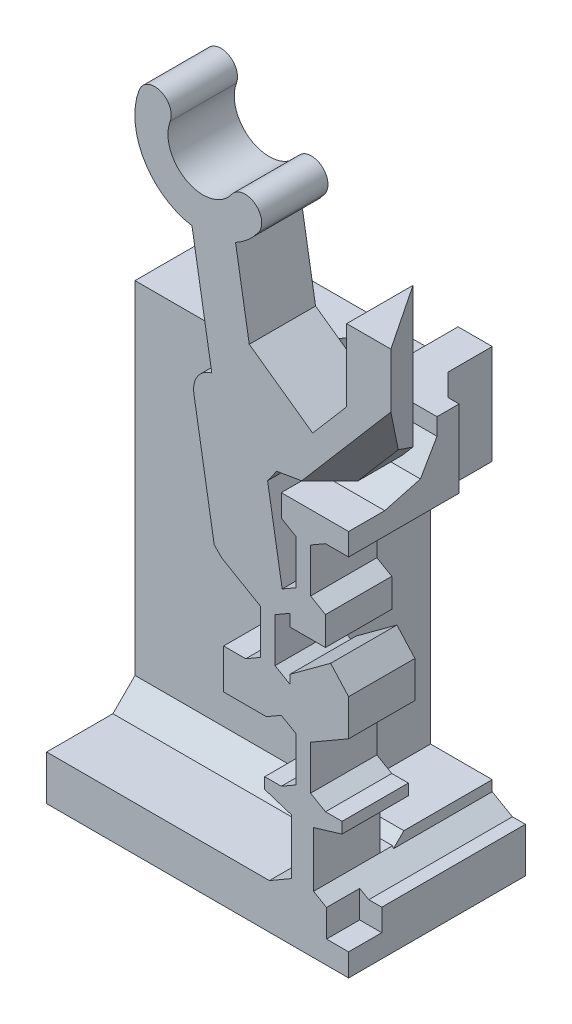
SolidWorks part; units mm, degrees
material "Nylon 6/12"
ref_plane "Front Plane" through (0, 0, 0) normal (0, 0, 1) x (1, 0, 0)
ref_plane "Top Plane" through (0, 0, 0) normal (0, 1, 0) x (1, 0, 0)
ref_plane "Right Plane" through (0, 0, 0) normal (1, 0, 0) x (0, 0, -1)
sketch "Sketch-SkeletonConfigUp" plane through (0, 0, 0) normal (0, 0, 1) x (1, 0, 0)
  line L0 (0, 0) -> (0, -50000) construction
  line L1 (0, 0) -> (4.5811, 6.2164) construction
  line L2 (9.8143, 13.3177) -> (4.5811, 13.945) construction
  line L3 (4.5811, 13.945) -> (2.9713, 10.4094) construction
  line L4 (2.9713, 10.4094) -> (4.5811, 6.2164) construction
  line L5 (4.5811, 13.945) -> (6.2429, 19.1409) construction
  line L6 (2.9713, 10.4094) -> (0.0405, 27.8193) construction
  line L7 (4.5811, 6.2164) -> (9.8143, 13.3177) construction
  line L8 (-587.3593, -797.0242) -> (9.8143, 13.3177) construction
  dimension "D2" = 7.7221
  dimension "D3" = 8.8212
  dimension "D4" = 5.2707
  dimension "D5" = 119.553
  dimension "D6" = 3.8848
  dimension "D7" = 5.4552
  dimension "D8" = 17.6549
  dimension "D9" = 4.4914
  dimension "D10" = 6.745
  dimension "D11" = 145.964
  dimension "D12" = 143.612
sketch "Sketch-SkeletonConfigDown" plane through (0, 0, 0) normal (0, 0, 1) x (1, 0, 0)
  line L0 (0, 0) -> (0, -50000) construction
  line L1 (0, 0) -> (4.5811, 6.2164) construction
  line L2 (9.8143, 13.3177) -> (4.5811, 13.945) construction
  line L3 (4.5811, 13.945) -> (6.1909, 10.4094) construction
  line L4 (6.1909, 10.4094) -> (4.5811, 6.2164) construction
  line L5 (4.5811, 13.945) -> (1.753, 18.6098) construction
  line L6 (6.1909, 10.4094) -> (-8.8652, 19.6294) construction
  line L7 (4.5811, 6.2164) -> (9.8143, 13.3177) construction
  line L8 (-589.9357, -800.5203) -> (9.8143, 13.3177) construction
  dimension "D2" = 7.7221
  dimension "D3" = 8.8212
  dimension "D4" = 5.2707
  dimension "D5" = 119.553
  dimension "D6" = 3.8848
  dimension "D7" = 5.4552
  dimension "D8" = 17.6549
  dimension "D9" = 4.4914
  dimension "D10" = 6.745
  dimension "D11" = 145.964
  dimension "D1" = 143.612
ref_plane "Plane-Cam Base" through (9.128, 0, 0) normal (1, 0, 0) x (0, 0, -1)
ref_plane "Plane-Down-to-Up Derailleur Clearance" through (6.628, 0, 0) normal (1, 0, 0) x (0, 0, -1)
ref_plane "Plane-Cam Cavity Roof" through (5.128, 0, 0) normal (1, 0, 0) x (0, 0, -1)
sketch "Sketch-SwitchBossUp" plane through (0, 0, 0) normal (0, 0, 1) x (1, 0, 0)
  line L0 (3.5811, 11.4759) -> (3.5811, 12.945) construction
  line L2 (6.5405, 21.1774) -> (6.5405, 24.4384)
  line L3 (6.5405, 24.4384) -> (8.5405, 24.4384)
  line L4 (8.5405, 24.4384) -> (8.5405, 20.4384)
  line L5 (5.5811, 12.5552) -> (5.5811, 11.263)
  line L7 (1.5115, 25.1048) -> (2.5464, 18.9575)
  line L8 (-0.4607, 24.7728) -> (0.4359, 19.4465)
  line L9 (2.9713, 10.4094) -> (0.0405, 27.8193) construction
  line L11 (-0.0396, 22.2712) -> (1.9326, 22.6032) construction
  line L15 (6.628, -23.7286) -> (6.628, 23.7286) construction
  line L16 (2.9713, 10.4094) -> (4.5811, 6.2164) construction
  line L17 (3.5811, 12.945) -> (3.5811, 14.945) construction
  line L18 (5.5811, 12.945) -> (5.5811, 14.945) construction
  line L19 (4.2561, 13.945) -> (4.9061, 13.945) construction
  line L20 (3.5811, 14.945) -> (5.5811, 14.945) construction
  line L21 (3.5811, 12.945) -> (5.5811, 12.945) construction
  line L22 (4.5811, 12.945) -> (4.5811, 14.945) construction
  line L23 (4.5811, 6.2164) -> (8.5405, 7.1023) construction
  line L24 (1.9713, 9.4094) -> (1.9713, 11.4094) construction
  line L25 (3.9713, 9.4094) -> (3.9713, 11.4094) construction
  line L26 (3.9713, 9.4094) -> (1.9713, 9.4094) construction
  line L27 (1.9713, 11.4094) -> (3.9713, 11.4094) construction
  line L28 (3.5811, 7.2164) -> (5.5811, 7.2164) construction
  line L29 (3.5811, 7.2164) -> (3.5811, 5.2164) construction
  line L30 (5.5811, 7.2164) -> (5.5811, 5.2164) construction
  line L31 (3.5811, 5.2164) -> (5.5811, 5.2164) construction
  line L32 (4.9061, 6.2164) -> (4.2561, 6.2164) construction
  line L40 (3.2963, 10.4094) -> (2.6463, 10.4094) construction
  line L43 (2.874, 4.5093) -> (0.7934, 4.5093) construction
  line L46 (5.0405, 1.437) -> (5.0405, 3.937)
  line L51 (4.9929, 19.3693) -> (2.5464, 18.9575)
  line L66 (0.0405, 27.8193) -> (0.0405, 50027.8193) construction
  line L74 (0.5455, 12.7717) -> (-0.3728, 18.2264)
  line L75 (0.3841, 13.7302) -> (2.3564, 14.0622) construction
  line L76 (5.5811, 11.263) -> (5.5811, 12.5552) construction
  line L77 (5.5811, 7.6061) -> (6.628, 8.2105)
  line L80 (5.8152, 10.763) -> (6.628, 9.8603)
  line L81 (8.5405, 1033.6218) -> (8.5405, 20.4384) construction
  line L82 (2.5464, 18.9575) -> (3.5585, 12.945) construction
  line L83 (3.6203, 12.5779) -> (2.8784, 16.9852)
  line L84 (2.8784, 16.9852) -> (6.0405, 17.5175)
  line L85 (6.9307, 9.5241) -> (8.5405, 7.7363) construction
  line L88 (3.5811, 16.3347) -> (6.8573, 16.3347)
  line L92 (3.7762, 8.3129) -> (6.9307, 9.5241) construction
  line L93 (6.3311, 4.3267) -> (5.0405, 3.937)
  line L95 (2.5464, 18.9575) -> (2.8784, 16.9852) construction
  line L96 (2.7124, 17.9713) -> (8.5405, 18.9524) construction
  line L97 (2.7124, 17.9713) -> (1.7262, 17.8053) construction
  line L98 (1.9713, 9.0197) -> (0.9713, 9.0197)
  line L99 (0.9713, 9.0197) -> (0.9713, 7.2164)
  line L100 (0.9713, 7.2164) -> (2.9061, 7.2164)
  line L101 (4.5811, 6.2164) -> (6.9307, 9.5241) construction
  line L103 (0.0405, 27.8193) -> (1.9448, 26.4638) construction
  line L104 (6.9307, 9.5241) -> (8.5405, 7.7363) construction
  line L106 (13.4416, 14.945) -> (5.5811, 14.945) construction
  line L107 (1.9713, 9.4094) -> (1.9713, 9.0197) construction
  line L109 (0.0405, 27.8193) -> (-2.1498, 28.6358) construction
  line L110 (8.5405, 20.4384) -> (6.0405, 17.5175)
  line L111 (6.628, 9.8603) -> (6.628, 8.2105)
  line L112 (6.628, 9.8603) -> (6.9307, 9.5241) construction
  line L113 (2.8311, 4.8267) -> (2.8311, 4.3267)
  line L114 (7.3693, 7.7363) -> (7.3563, 7.7363) construction
  line L115 (6.8573, 16.3347) -> (13.4416, 16.3347)
  line L116 (13.4416, 16.3347) -> (13.4416, -1.1653)
  line L117 (13.4416, -1.1653) -> (5.0405, -1.1653)
  line L119 (10.4375, 14.0252) -> (10.4375, 2.1692)
  line L121 (5.0405, -1.1653) -> (5.0405, 1.437) construction
  line L122 (8.237, 12.8031) -> (10.8393, 12.8031) construction
  line L123 (10.8393, 12.8031) -> (13.4416, 12.8031) construction
  line L124 (10.4375, 2.1692) -> (9.128, 0.8597)
  line L125 (8.5405, 7.5847) -> (13.4416, 7.5847) construction
  line L127 (5.5811, 15.3347) -> (5.5811, 14.945) construction
  line L130 (6.0405, 0.8597) -> (9.128, 0.8597)
  line L132 (2.8311, 4.3267) -> (4.0405, 3.937)
  line L133 (2.9713, 10.4094) -> (6.1909, 10.4094) construction
  line L134 (4.5811, 10.4094) -> (4.5811, 13.945) construction
  line L135 (4.5811, 10.4094) -> (4.5811, 6.2164) construction
  line L136 (0.8973, 12.4192) -> (0.5455, 12.7717)
  line L137 (3.9713, 9.4094) -> (5.5811, 7.2164) construction
  line L139 (5.8152, 10.763) -> (3.9713, 9.4094)
  line L140 (4.0405, 3.937) -> (4.0405, 1.437)
  line L141 (4.0405, 1.437) -> (3.0405, 0.8597)
  line L142 (3.0405, 0.8597) -> (3.0405, -1.1653)
  line L143 (8.5405, 20.4384) -> (8.5405, 18.9524) construction
  line L145 (8.5405, 17.9384) -> (8.5405, -49992.0368) construction
  line L147 (5.5811, 11.263) -> (5.5811, 12.5552) construction
  line L149 (6.3311, 4.8267) -> (6.3311, 4.3267)
  line L150 (3.0405, -1.1653) -> (5.0405, -1.1653)
  line L151 (4.0405, 3.937) -> (5.0405, 3.937) construction
  line L152 (4.2561, 14.945) -> (4.2561, 12.945)
  line L153 (4.9061, 14.945) -> (4.9061, 12.945)
  line L155 (4.2561, 14.945) -> (3.5811, 15.3347)
  line L156 (4.9061, 14.945) -> (5.5811, 15.3347)
  line L157 (3.5811, 16.3347) -> (3.5811, 15.3347)
  line L158 (5.5811, 15.3347) -> (9.128, 15.3347)
  line L162 (3.2963, 11.4094) -> (3.2963, 9.4094)
  line L164 (2.6463, 11.4094) -> (2.6463, 9.4094)
  line L169 (4.2561, 7.2164) -> (4.2561, 5.2164)
  line L170 (4.9061, 5.2164) -> (4.9061, 7.2164)
  line L175 (4.2561, 7.2164) -> (3.5811, 7.6061)
  line L176 (4.9061, 7.2164) -> (5.5811, 7.6061)
  line L177 (5.5811, 7.2164) -> (5.5811, 7.6061) construction
  line L179 (4.2561, 5.2164) -> (3.5811, 4.8267)
  line L180 (3.5811, 5.2164) -> (3.5811, 4.8267) construction
  line L181 (3.5811, 4.8267) -> (2.8311, 4.8267)
  line L183 (4.9061, 5.2164) -> (5.5811, 4.8267)
  line L184 (5.5811, 5.2164) -> (5.5811, 4.8267) construction
  line L186 (9.128, -23.7286) -> (9.128, 23.7286) construction
  line L187 (2.6463, 9.4094) -> (1.9713, 9.0197)
  line L188 (3.2963, 9.4094) -> (3.9713, 9.0197)
  line L189 (3.2963, 11.4094) -> (3.9713, 11.7991)
  line L190 (2.6463, 11.4094) -> (0.8973, 12.4192)
  line L191 (3.9713, 11.4094) -> (3.9713, 11.7991) construction
  line L192 (3.9713, 11.7991) -> (3.9713, 11.263)
  line L193 (4.9061, 12.945) -> (5.5811, 12.5552)
  line L194 (4.2561, 12.945) -> (3.6203, 12.5779)
  line L195 (3.9713, 11.263) -> (5.5811, 11.263)
  line L196 (3.9713, 9.4094) -> (3.9713, 9.0197)
  line L197 (3.5811, 7.2164) -> (3.5811, 7.6061) construction
  line L199 (3.5811, 7.6061) -> (2.9061, 7.2164)
  line L200 (5.5811, 4.8267) -> (6.3311, 4.8267)
  line L201 (2.8311, 4.3267) -> (2.8311, 3.937) construction
  line L202 (2.8311, 3.937) -> (4.0405, 3.937) construction
  line L203 (10.4375, 14.0252) -> (9.128, 15.3347)
  line L204 (4.0405, 1.437) -> (3.0405, 1.437) construction
  line L205 (3.0405, 1.437) -> (3.0405, 0.8597) construction
  line L206 (5.0405, 1.437) -> (6.0405, 0.8597)
  line L207 (8.5405, 18.9524) -> (8.5405, 17.9384) construction
  line L208 (6.0405, 17.5175) -> (8.5405, 17.9384) construction
  line L209 (8.5405, 20.4384) -> (8.5405, 17.9384) construction
  line L210 (6.5405, 21.1774) -> (4.9929, 19.3693)
  arc A0 (1.5115, 25.1048) -> (2.5558, 26.0289) centre (0.0405, 27.8193) ccw
  arc A1 (-0.4607, 24.7728) -> (-2.8525, 28.8978) centre (0.0405, 27.8193) cw
  arc A2 (-2.8525, 28.8978) -> (-1.447, 28.3738) centre (-2.1498, 28.6358) cw
  arc A3 (2.5558, 26.0289) -> (1.3338, 26.8987) centre (1.9448, 26.4638) ccw
  arc A4 (-1.447, 28.3738) -> (1.3338, 26.8987) centre (0.0405, 27.8193) ccw
  arc A5 (3.5811, 12.945) -> (3.5811, 14.945) centre (3.1778, 13.945) ccw construction
  arc A6 (5.5811, 12.945) -> (5.5811, 14.945) centre (5.9843, 13.945) cw construction
  arc A7 (2.5293, 9.921) -> (1.9713, 11.4094) centre (1.568, 10.4094) ccw construction
  arc A8 (3.9713, 11.4094) -> (3.9713, 9.4094) centre (4.3745, 10.4094) ccw construction
  arc A9 (3.5811, 7.2164) -> (3.5811, 5.2164) centre (3.1779, 6.2164) cw construction
  arc A10 (5.5811, 7.2164) -> (5.5811, 5.2164) centre (5.9844, 6.2164) ccw construction
  arc A19 (-0.3728, 18.2264) -> (0.4359, 19.4465) centre (0.6836, 18.4042) cw
  circle A28 centre (0.0405, 27.8193) radius 2.3375 construction
  arc A29 (1.9713, 9.4094) -> (2.5293, 9.921) centre (1.568, 10.4094) ccw construction
  point P53 (4.5811, 13.945)
  point P63 (2.9713, 10.4094)
  point P93 (0.9465, 22.4372)
  dimension "D23" = 1.5875
  dimension "D24" = 0.75
  dimension "D2" = 2
  dimension "D5" = 2
  dimension "D6" = 0.65
  dimension "D8" = 42
  dimension "D7" = 2
  dimension "D10" = 5
  dimension "D11" = 8.5
  dimension "D14" = 7.5
  dimension "D4" = 3
  dimension "D16" = 42
  dimension "D12" = 1
  dimension "D13" = 2.5
  dimension "D25" = 120
  dimension "D26" = 120
  dimension "D27" = 120
  dimension "D28" = 120
  dimension "D29" = 120
  dimension "D30" = 120
  dimension "D31" = 120
  dimension "D32" = 120
  dimension "D33" = 120
  dimension "D34" = 120
  dimension "D35" = 120
  dimension "D36" = 120
  dimension "D17" = 0.5
  dimension "D20" = 3.5
  dimension "D21" = 1
  dimension "D18" = 45
  dimension "D9" = 17.5
  dimension "D22" = 1
  dimension "D19" = 120
  dimension "D37" = 120
  dimension "D15" = 45
  dimension "D38" = 2
  dimension "D39" = 0.5
  dimension "D40" = 60
  dimension "D41" = 1
  dimension "D42" = 45
  dimension "D43" = 120
  dimension "D44" = 2
  dimension "D45" = 2.5
  dimension "D46" = 2.5
  dimension "D47" = 4
  dimension "D48" = 2
extrude "Boss-Switch Main" add sketch "Sketch-SwitchBossUp" along normal blind 3
sketch "Sketch1" plane through (0, 0, 0) normal (0, 0, -1) x (-1, 0, 0)
  line L0 (-3.5811, 16.3347) -> (-3.5811, 15.3347) construction
  line L1 (-7.5811, -1.1653) -> (0.4122, -1.1653)
  line L2 (-7.5811, -1.1653) -> (-7.5811, 0.8597)
  line L4 (0.4122, -1.1653) -> (0.4122, 0.8597)
  line L5 (-3.5811, 18.8347) -> (-7.5811, 18.8347)
  line L10 (-7.5811, 18.8347) -> (-7.5811, 15.3347)
  line L11 (-4.0405, 1.437) -> (-5.0405, 1.437)
  line L12 (-7.5811, 15.3347) -> (-3.5811, 15.3347)
  line L13 (-4.0405, 1.437) -> (-3.0405, 0.8597)
  line L14 (-3.5811, 15.3347) -> (-3.5811, 18.8347)
  line L22 (-3.0405, -1.1653) -> (-13.4416, -1.1653) construction
  line L23 (-3.0405, 0.8597) -> (0.4122, 0.8597)
  line L24 (-5.0405, 1.437) -> (-6.0405, 0.8597)
  line L25 (-6.0405, 0.8597) -> (-7.5811, 0.8597)
  line L26 (-9.128, 15.3347) -> (-5.5811, 15.3347) construction
  dimension "D1" = 3.5
  dimension "D4" = 4
extrude "Boss-Flange Width" add sketch "Sketch1" along normal blind 5
ref_plane "Plane-Sta2Sit Groove" through (0.0405, 0, 0) normal (1, 0, 0) x (0, 0, -1)
ref_plane "Plane-Cam Outer Surface" through (-12.0395, 0, 0) normal (1, 0, 0) x (0, 0, -1)
ref_plane "Plane-FlangeTop" through (-7.0395, 0, 0) normal (1, 0, 0) x (0, 0, -1)
sketch "Sketch2" plane through (-7.0395, 0, 0) normal (1, 0, 0) x (0, 0, -1)
  line L0 (5, 15.3347) -> (0, 15.3347) construction
  line L1 (5, 17.3347) -> (1, 17.3347)
  line L2 (5, 17.3347) -> (5, 15.3347)
  line L3 (5, 15.3347) -> (1, 15.3347)
  line L4 (1, 17.3347) -> (1, 15.3347)
  line L10 (-3, -1.1653) -> (-3, 16.3347) construction
  line L11 (5, 0.8597) -> (-3, 0.8597)
  line L12 (5, 0.8597) -> (5, -1.1653)
  line L13 (5, -1.1653) -> (-3, -1.1653)
  line L14 (-3, 0.8597) -> (-3, -1.1653)
  line L15 (0, 10.4094) -> (0, 27.8193) construction
  line L17 (5, 0.8597) -> (5, -1.1653) construction
  line L18 (-3, 0.8597) -> (0, 0.8597) construction
  dimension "D1" = 1
  dimension "D2" = 2
extrude "Boss-Flange Height" add sketch "Sketch2" along normal up to surface (11.6675 mm away)
sketch "Sketch10" plane through (0, 15.3347, 0) normal (0, 1, 0) x (1, 0, 0)
  line L0 (9.128, -23.7286) -> (9.128, 23.7286) construction
  line L1 (7.5811, 5) -> (5.128, 5)
  line L2 (7.5811, 5) -> (7.5811, 2)
  line L3 (7.5811, 2) -> (5.128, 2)
  line L5 (4.628, 7) -> (4.628, 1) construction
  line L6 (3.5811, 1) -> (-7.0395, 1) construction
  line L8 (5.128, 5) -> (5.128, 2)
  dimension "D1" = 1
  dimension "D2" = 0.5
  dimension "D3" = 4.5
extrude "Cut-Up-To-Down Derailleur Clearance" cut sketch "Sketch10" along normal up to next
sketch "Sketch17" plane through (0, 15.3347, 0) normal (0, -1, 0) x (1, 0, 0)
  line L0 (5.128, -5) -> (-7.0395, -5)
  line L1 (5.128, -5) -> (3.5811, -5) construction
  line L2 (-7.0395, -5) -> (-7.0395, -1)
  line L3 (-7.0395, -1) -> (5.128, -1)
  line L4 (5.128, -1) -> (5.128, -5)
  line L5 (-7.0395, -1) -> (-7.0395, -5) construction
extrude "Boss-Flange Support" add sketch "Sketch17" along normal up to surface (14.475 mm away) up to face at (-1.9995, 0.8597, -1)
sketch "Sketch-HolePositions" plane through (0, -1.1653, 0) normal (0, -1, 0) x (1, 0, 0)
  line L0 (-7.0395, -3) -> (7.5811, -3) construction
  line L1 (7.5811, -5) -> (-7.0395, -5) construction
  line L2 (7.5811, -5) -> (7.5811, 0) construction
  line L4 (-7.0395, -22.2167) -> (-7.0395, 22.2167) construction
  line L5 (3.5811, -1) -> (3.5811, -5) construction
  point P6 (-4.0395, -3)
  point P7 (0.5811, -3)
  dimension "D1" = 3
  dimension "D2" = 3
  dimension "D3" = 2
sketch "Sketch6" plane through (0, -1.1653, 0) normal (0, -1, 0) x (-1, 0, 0)
  point P0 (4.0395, 3)
  point P3 (-0.5811, 3)
hole_wizard "Tap Drill for M2x0.4 Tap1" positions "Sketch6" profile "Sketch5" hole size "M2x0.4" standard "ANSI Metric" end condition through all
sketch "Sketch5" plane through (-4.0395, -1.1653, -3) normal (1, 0, 0) x (0, 0, -1)
  line L0 (0, 0) -> (0, 30.5511)
  line L1 (0, 30.5511) -> (0.8, 30.5511)
  line L2 (0.8, 30.5511) -> (0.8, 0)
  line L5 (0.8, 0) -> (0, 0)
  line L11 (0, -6.35) -> (0, 107.95) construction
  dimension "Thru Hole Dia." = 1.6
  dimension "Thru Hole Depth" = 30.5511
sketch "Sketch9" plane through (0, -1.1653, 0) normal (0, -1, 0) x (1, 0, 0)
  point P0 (-4.0395, -3)
  point P3 (0.5811, -3)
hole_wizard "M2 Clearance Hole2" positions "Sketch9" profile "Sketch8" hole size "M2" standard "ANSI Metric"
sketch "Sketch8" plane through (-4.0395, -1.1653, -3) normal (1, 0, 0) x (0, 0, -1)
  line L0 (0, 0) -> (0, 15.721)
  line L1 (0, 15.721) -> (1.2, 15)
  line L2 (1.2, 15) -> (1.2, 0)
  line L5 (1.2, 0) -> (0, 0)
  line L10 (0, 15.721) -> (-1.2, 15) construction
  line L11 (0, -6.35) -> (0, 107.95) construction
  dimension "Hole Dia." = 2.4
  dimension "Hole Depth" = 15
  dimension "Drill Angle" = 118
sketch "Sketch-Measurements for Derailleur Ramps" plane through (0, 0, 0) normal (0, 0, 1) x (1, 0, 0)
  line L0 (2.8784, 16.9852) -> (2.5464, 18.9575)
  line L1 (2.7124, 17.9713) -> (1.7262, 17.8053)
  line L2 (2.9713, 10.4094) -> (0.0405, 27.8193) construction
  line L3 (1.7262, 17.8053) -> (-1.8937, 15.3603)
  line L4 (6.1909, 10.4094) -> (-8.8652, 19.6294) construction
  line L5 (1.7262, 17.8053) -> (2.6012, 12.6077)
  line L6 (2.6012, 12.6077) -> (-1.8937, 15.3603)
  line L7 (-0.0837, 16.5828) -> (-0.0837, 17.8053)
  line L8 (-0.0837, 17.8053) -> (1.7262, 17.8053)
  line L9 (6.1909, 10.4094) -> (2.9713, 10.4094)
  line L10 (5.386, 8.3129) -> (3.7762, 8.3129)
  line L12 (6.1909, 10.4094) -> (4.5811, 6.2164) construction
  line L13 (4.5811, 8.3129) -> (4.5811, 8.7912)
  line L14 (4.5811, 6.2164) -> (5.386, 8.3129)
  line L15 (2.9713, 10.4094) -> (4.5811, 6.2164) construction
  line L16 (3.7762, 8.3129) -> (4.5811, 6.2164)
  line L17 (5.386, 8.3129) -> (5.386, 8.7912)
  dimension "D1" = 1.81
  dimension "D2" = 0.8049
sketch "Sketch12" plane through (0, 24.4384, 0) normal (0, 1, 0) x (1, 0, 0)
  line L0 (6.5405, 0) -> (8.5405, -3)
  line L1 (8.5405, -3) -> (8.5405, 0)
  line L2 (8.5405, 0) -> (6.5405, 0)
extrude "Cut-Up-to-Down Cantilever Slope" cut sketch "Sketch12" against normal up to next
ref_plane "Plane1" through (0, 7.1023, 0) normal (0, 1, 0) x (1, 0, 0)
sketch "Sketch-Derailleur Location" plane through (0, 7.1023, 0) normal (0, 1, 0) x (1, 0, 0)
  line L0 (8.5405, 0) -> (8.5405, -3)
  line L1 (4.0405, -3) -> (3.0405, -3) construction
  line L2 (-119237.4187, 0) -> (9.8143, 0) construction
  point P0 (8.5405, 0)
  point P8 (8.5405, -1.5)
ref_plane "Plane-Cantilever Cut" [suppressed] through (7.0848, 8.5204, -1.9058) normal (-0.6301, -0.7578, 0.1695) x (-0.7765, 0.6151, -0.1368)
sketch "Sketch14" [suppressed] plane through (7.0848, 8.5204, -1.9058) normal (-0.6301, -0.7578, 0.1695) x (-0.7765, 0.6151, -0.1368)
  line L0 (2.3023, -1.6911) -> (-0.3551, -1.6911)
  line L2 (2.3023, -4.3362) -> (2.3023, -1.6911)
  line L3 (-0.3551, -1.6911) -> (-0.3551, -4.4608)
  line L5 (-0.3551, -4.4608) -> (1.0087, -5.0843)
  line L6 (1.0087, -5.0843) -> (2.3023, -4.3362)
extrude "Cut-Down-to-Up Cantilever Slope" [suppressed] cut sketch "Sketch14" against normal up to next
sketch "Sketch16" plane through (0, 0, 0) normal (0, 0, -1) x (-1, 0, 0)
  line L0 (-7.5811, 18.8347) -> (-13.4416, 18.8347)
  line L1 (-13.4416, 18.8347) -> (-13.4416, -1.1653)
  line L2 (-13.4416, -1.1653) -> (-6.628, -1.1653)
  line L3 (-13.4416, -1.1653) -> (-5.0405, -1.1653) construction
  line L4 (-6.628, -1.1653) -> (-6.628, 5.2038)
  line L5 (-6.628, 5.2038) -> (-8.0037, 5.2038)
  line L6 (-8.0037, 5.2038) -> (-8.0037, 12.0484)
  line L7 (-8.0037, 12.0484) -> (-6.628, 12.0484)
  line L8 (-6.628, 12.0484) -> (-6.628, 17.9477)
  line L9 (-6.628, 23.7286) -> (-6.628, -23.7286) construction
  line L10 (-3.5811, 18.8347) -> (-6.5405, 18.8347) construction
  line L11 (-7.5811, 18.8347) -> (-6.628, 17.9477)
extrude "Cut-Down-to-Up Derailleur Clearance" cut sketch "Sketch16" against normal through all and the other way through all
ref_plane "Plane-Symmetry Plane" through (0, 0, 1.5) normal (0, 0, 1) x (1, 0, 0)
sketch "Sketch-Cable Center Point" plane through (0, 0, 1.5) normal (0, 0, 1) x (1, 0, 0)
  line L0 (0.0405, 27.8193) -> (0.1722, 27.0366)
  line L1 (2.9713, 10.4094) -> (0.0405, 27.8193) construction
  point P0 (0.0405, 27.8193)
  dimension "D1" = 0.7937
chamfer "Chamfer-Flange Support" distance 1.5 angle 45 1 edges at (3.5811, 17.3347, -3)
chamfer "Chamfer-Flange Support 2" distance 1 angle 45 2 edges at (5.128, 17.0847, -2) (5.128, 15.3347, -1.5)
chamfer "Chamfer-Flange Support 3" distance 1 angle 45 1 edges at (-1.9995, 0.8597, -1)
sketch "Sketch18" plane through (6.628, 0, 0) normal (1, 0, 0) x (0, 0, -1)
  line L1 (-3, -0.1403) -> (-1.5, -0.1403)
  line L2 (-3, -0.1403) -> (-3, 1.437)
  line L3 (-3, 1.437) -> (-1.5, 1.437)
  line L4 (-1.5, -0.1403) -> (-1.5, 1.437)
  line L5 (0.5774, 1.437) -> (0, 1.437) construction
  line L6 (-3, -1.1653) -> (-3, 0.8597) construction
  line L7 (-3, 0.8597) -> (5, 0.8597) construction
  dimension "D1" = 1.5
  dimension "D2" = 1
extrude "Cut-Down-to-Up Derailleur Clearance 2" cut sketch "Sketch18" against normal blind 1
sketch "Sketch19" plane through (0, 0, 0) normal (0, 0, 1) x (1, 0, 0)
  line L7 (3.5811, 18.8347) -> (6.628, 18.8347)
  line L8 (6.628, 18.8347) -> (6.628, 16.3347)
  line L9 (6.628, 16.3347) -> (3.5811, 16.3347)
  line L10 (3.5811, 16.3347) -> (3.5811, 18.8347)
  line L11 (6.628, 16.3347) -> (6.628, 17.9477) construction
extrude "Cut-Up-to-Down Cantilever Clearance" cut sketch "Sketch19" against normal up to surface (1 mm away) up to face at (1.4435, 12.7784, -1)
chamfer "Chamfer1" distance 1 angle 60 1 edges at (5.1045, 16.3347, -1) first distance on face at (5.1045, 16.3347, 1)
chamfer "Chamfer3" distance 0.75 angle 60 1 edges at (3.5811, 16.7007, -1) first distance on face at (3.5811, 16.1233, 0.6667)
chamfer "Chamfer4" distance 0.5 angle 60 1 edges at (4.205, 15.3347, -1) first distance on face at (5.1242, 15.3347, -0.0278)
chamfer "Chamfer5" distance 0.5 angle 45 1 edges at (2.8784, 16.9852, 1.5)
chamfer "Chamfer6" distance 2.5 angle 45 1 edges at (2.5464, 18.9575, 1.5)
chamfer "Chamfer7" distance 1 angle 45 1 edges at (7.2905, 18.978, 3)
sketch "Sketch22" plane through (0, 0, 0) normal (0, 0, 1) x (1, 0, 0)
  line L0 (6.628, 17.9477) -> (7.5811, 18.8347) construction
  line L1 (6.628, 18.8347) -> (7.5811, 18.8347) construction
  line L2 (6.628, 17.9477) -> (6.628, 18.8347) construction
  line L3 (6.628, 17.9477) -> (7.5811, 18.8347)
  line L4 (6.628, 18.8347) -> (7.5811, 18.8347)
  line L5 (6.628, 17.9477) -> (6.628, 18.8347)
extrude "Cut-Extrude3" cut sketch "Sketch22" against normal up to next
chamfer "Chamfer8" distance 0.5 angle 45 1 edges at (5.1045, 16.3347, 0) first distance on face at (4.2965, 17.2286, -0.5161)
sketch "Sketch23" plane through (0, 0, -1) normal (0, 0, 1) x (1, 0, 0)
  line L0 (5.128, 1.8597) -> (2.3369, 1.8597)
  line L1 (-7.0395, 1.8597) -> (5.128, 1.8597) construction
  line L2 (2.3369, 1.8597) -> (2.3369, 14.3347)
  line L3 (2.3369, 14.3347) -> (5.128, 14.3347)
  line L4 (5.128, 14.3347) -> (5.128, 1.8597)
extrude "Cut-Extrude4" cut sketch "Sketch23" against normal through all
equation "\"axle-diameter\"=2"
equation "\"switch-thickness\"=12"
equation "\"base-width\"=4.0"
equation "\"axle-bushing-radius\"=3"
equation "\"clearance\"= 0.25"
equation "\"arm-width\"=1.5"
equation "\"min-diameter\"=70"
equation "\"alpha\"=143.6120"
equation "\"gamma\"=119.5526"
equation "\"delta\"=145.9637"
equation "\"epsilon\"=6.7452"
equation "\"l_AB\"=8.8212"
equation "\"l_AC\"=4.4914"
equation "\"l_BD\"=5.2707"
equation "\"l_CD\"=3.8848"
equation "\"l_CE\"=17.6549"
equation "\"l_DF\"=5.4552"
equation "\"l_OA\"=7.7221"
equation "\"D2@Sketch-SkeletonConfigUp\" = \"l_OA\""
equation "\"D3@Sketch-SkeletonConfigUp\" = \"l_AB\""
equation "\"D4@Sketch-SkeletonConfigUp\" = \"l_BD\""
equation "\"D5@Sketch-SkeletonConfigUp\" = \"gamma\""
equation "\"D6@Sketch-SkeletonConfigUp\" = \"l_CD\""
equation "\"D7@Sketch-SkeletonConfigUp\" = \"l_DF\""
equation "\"D8@Sketch-SkeletonConfigUp\" = \"l_CE\""
equation "\"D9@Sketch-SkeletonConfigUp\" = \"l_AC\""
equation "\"D_groove\"=3.175"
equation "\"D7@Sketch-SkeletonConfigDown\" = \"l_DF\""
equation "\"D6@Sketch-SkeletonConfigDown\" = \"l_CD\""
equation "\"D2@Sketch-SkeletonConfigDown\" = \"l_OA\""
equation "\"D3@Sketch-SkeletonConfigDown\" = \"l_AB\""
equation "\"D9@Sketch-SkeletonConfigDown\" = \"l_AC\""
equation "\"D8@Sketch-SkeletonConfigDown\" = \"l_CE\""
equation "\"D5@Sketch-SkeletonConfigDown\" = \"gamma\""
equation "\"D4@Sketch-SkeletonConfigDown\" = \"l_BD\""
equation "\"D1@Sketch-SkeletonConfigDown\" = \"alpha\""
equation "\"hinge_length\"=1.5"
equation "\"hinge_depth\"=0.25"
equation "\"D10@Sketch-SkeletonConfigUp\"=\"epsilon\""
equation "\"D11@Sketch-SkeletonConfigUp\"=\"delta\""
equation "\"D12@Sketch-SkeletonConfigUp\"=\"alpha\""
equation "\"D11@Sketch-SkeletonConfigDown\"=\"delta\""
equation "\"D10@Sketch-SkeletonConfigDown\"=\"epsilon\""
equation "\"EE_dx\"=8.9056"
equation "\"EE_dy\"=8.1898"
equation "\"r_groove\"=\"D_groove\"/2"
equation "\"t_wall\"=25.4/16"
equation "\"width_lower\"=\"D_groove\"+\"t_wall\""
equation "\"cable_to_bottom\"=30.6257"
equation "\"switch_EE-up_base_dy\"=24"
equation "\"switch_EE-down_base_dy\"=16"
equation "\"D_axle\"=25.4/8"
equation "\"D_up_to_down\"=16"
equation "\"D_down_to_up\"=25"
equation "\"t_cam_base\"=7.5"
equation "\"D23@Sketch-SwitchBossUp\"=\"D_groove\"/2"
equation "\"D1@Sketch-Cable Center Point\"=\"D_groove\"/4"
